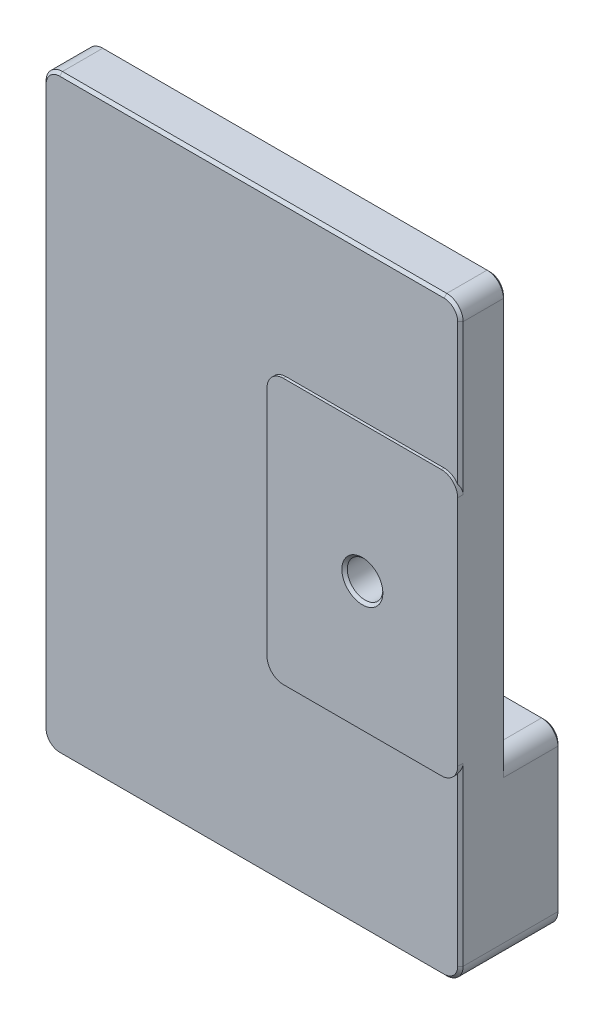
SolidWorks part; units mm, degrees
material "ABS"
ref_plane "Front Plane" through (0, 0, 0) normal (0, 0, 1) x (1, 0, 0)
ref_plane "Top Plane" through (0, 0, 0) normal (0, 1, 0) x (1, 0, 0)
ref_plane "Right Plane" through (0, 0, 0) normal (1, 0, 0) x (0, 0, -1)
sketch "Sketch1" plane through (0, 0, 0) normal (0, 0, 1) x (1, 0, 0)
  line L0 (127, 38.1) -> (-127, 38.1) construction
  line L1 (121.9, 38.1) -> (45.3397, 38.1)
  line L2 (121.9, 38.1) -> (121.9, -70.4)
  line L3 (121.9, -70.4) -> (45.3397, -70.4)
  line L4 (45.3397, 38.1) -> (45.3397, -70.4)
  line L5 (45.3397, -70.4) -> (143.4603, -70.4) construction
  line L8 (45.3397, -67.4) -> (45.3397, -70.4) construction
  line L9 (121.9, -38.1) -> (45.3397, -38.1)
  line L10 (-127, -38.1) -> (127, -38.1) construction
  line L12 (121.9, 10.6) -> (86.9, 10.6)
  line L13 (121.9, 10.6) -> (121.9, -39.4)
  line L14 (121.9, -39.4) -> (86.9, -39.4)
  line L15 (86.9, 10.6) -> (86.9, -39.4)
  line L16 (104.4, -39.4) -> (104.4, 10.6) construction
  line L17 (121.9, -14.4) -> (86.9, -14.4) construction
  circle A0 centre (104.4, -14.4) radius 3.2639
  arc A1 (101.3632, -15.5963) -> (107.4368, -15.5963) centre (104.4, -14.4) ccw construction
  dimension "D1" = 35
  dimension "D2" = 50
extrude "Boss-Extrude1" add sketch "Sketch1" along normal up to surface (8.4 mm away) contours L2 L9 L4 L3 | L9 L2 L1 L4 A0 | L12 L15 L9 L13 A0 | L9 L15 L14 L13 region at (75.0424, 5.6756, 0) region at (121.3003, -13.75, 0) region at (83.2303, -54.5405, 0) region at (104.4, -38.75, 0)
extrude "Boss-Extrude2" add sketch "Sketch1<3>" along normal up to surface (8.9 mm away) contours L12 L15 L9 L13 A0 region at (121.3003, -13.75, 0)
sketch "Sketch1<3>" plane through (0, 0, 0) normal (0, 0, 1) x (1, 0, 0) same geometry as "Sketch1"
extrude "Boss-Extrude3" add sketch "Sketch1<4>" against normal blind 10 contours L15 L9 L4 L3 L2 L13 L14 | L9 L15 L14 L13 region at (83.2303, -54.5405, 0) region at (104.4, -38.75, 0)
sketch "Sketch1<4>" plane through (0, 0, 0) normal (0, 0, 1) x (1, 0, 0) same geometry as "Sketch1"
fillet "Fillet1" radius 3 10 edges at (86.9, 10.6, 8.65) (121.9, 10.6, 8.65) (86.9, -38.1, 8.65) (121.9, -38.1, 8.65) (45.3397, 38.1, 4.2) (121.9, 38.1, 4.2) (45.3397, -38.1, -5) (121.9, -38.1, -5) (45.3397, -70.4, -0.8) (121.9, -70.4, -0.8)
chamfer "Chamfer1" distance 0.5 angle 45 23 edges at (45.3397, -54.25, -10) (46.2184, -38.9787, -10) (46.2184, -69.5213, -10) (83.6199, -38.1, -10) (83.6199, -70.4, -10) (121.0213, -38.9787, -10) (121.0213, -69.5213, -10) (121.9, -54.25, -10) (107.6639, -14.4, 0) (121.9, -3, 0) (45.3397, -3, 0) (121.0213, 37.2213, 0) (46.2184, 37.2213, 0) (83.6199, 38.1, 0) (104.4, -17.6639, 8.9) (83.6199, -70.4, 8.4) (46.2184, -69.5213, 8.4) (121.0213, -69.5213, 8.4) (45.3397, -16.15, 8.4) (46.2184, 37.2213, 8.4) (121.0213, 37.2213, 8.4) (83.6199, 38.1, 8.4) (121.9, 21.35, 8.4)
